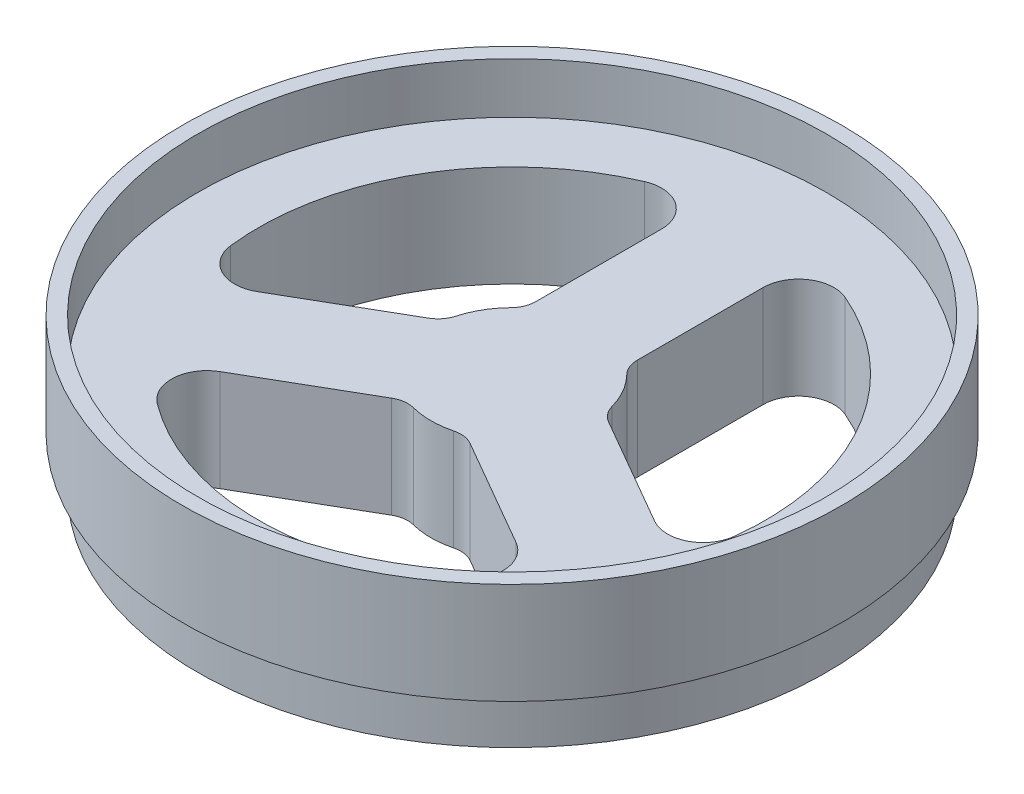
SolidWorks part; units mm, degrees
material "HYPALON"
ref_plane "Front Plane" through (0, 0, 0) normal (0, 0, 1) x (1, 0, 0)
ref_plane "Top Plane" through (0, 0, 0) normal (0, 1, 0) x (1, 0, 0)
ref_plane "Right Plane" through (0, 0, 0) normal (1, 0, 0) x (0, 0, -1)
sketch "Sketch1" plane through (0, 0, 0) normal (0, 0, 1) x (1, 0, 0)
  line L0 (0, 0) -> (0, 22.2877) construction
  line L1 (0, 0) -> (-62, 0)
  line L2 (-62, 0) -> (-62, 10)
  line L3 (-62, 10) -> (-65, 10)
  line L4 (-65, 10) -> (-65, 30)
  line L5 (-65, 30) -> (-62, 30)
  line L6 (-62, 30) -> (-62, 20)
  line L7 (-62, 20) -> (0, 20)
  line L8 (0, 20) -> (0, 0)
  point P3 (-62, 25)
  dimension "D1" = 20
  dimension "D2" = 10
  dimension "D3" = 10
  dimension "D4" = 3
  dimension "D5" = 65
  dimension "D6" = 3
revolve "Revolve1" add sketch "Sketch1" angle 360 about L0
sketch "Szkic1" plane through (0, 0, 0) normal (0, 1, 0) x (1, 0, 0)
  line L0 (0, 0) -> (-10, 0)
  line L1 (-10, 0) -> (0, 0)
  line L2 (0, 0) -> (10, 0)
  line L3 (-10, 0) -> (-10, 12.49)
  line L4 (10, 0) -> (10, 12.49)
  line L5 (5.8167, -14.9053) -> (37.4264, -33.1552)
  line L6 (-10, 12.49) -> (-10, 48.9898)
  line L7 (10, 12.49) -> (10, 48.9898)
  line L8 (15.8167, 2.4153) -> (47.4264, -15.8346)
  line L9 (-15.8167, 2.4153) -> (-47.4264, -15.8346)
  line L10 (-5.8167, -14.9053) -> (-37.4264, -33.1552)
  circle A0 centre (0, 0) radius 64
  circle A1 centre (0, 0) radius 50
  circle A2 centre (0, 0) radius 16
  point P22 (0, 0)
  dimension "D1" = 128
  dimension "D2" = 100
  dimension "D5" = 32
  dimension "D3" = 10
  dimension "D4" = 10
  dimension "D6" = 3
sketch "Szkic2" plane through (0, 0, 0) normal (0, 1, 0) x (1, 0, 0)
  circle A0 centre (0, 0) radius 35
  circle A1 centre (0, 0) radius 63
  dimension "D1" = 126
  dimension "D2" = 70
extrude "Cut-Extrude1" cut sketch "Szkic1" along normal up to surface (20 mm away) contours A2 L6 A1 L9 | A2 L8 A1 L7 | A2 L10 A1 L5 region at (-29.0728, 0, -16.7852) region at (29.0728, 0, -16.7852) region at (0, 0, 33.5704) up to face at (0, 20, -62)
fillet "Fillet1" radius 5 6 edges at (-15.8167, 10, -2.4153) (-10, 10, -12.49) (10, 10, -12.49) (15.8167, 10, -2.4153) (5.8167, 10, 14.9053) (-5.8167, 10, 14.9053)
fillet "Fillet2" radius 7 6 edges at (37.4264, 10, 33.1552) (47.4264, 10, 15.8346) (10, 10, -48.9898) (-10, 10, -48.9898) (-47.4264, 10, 15.8346) (-37.4264, 10, 33.1552)
